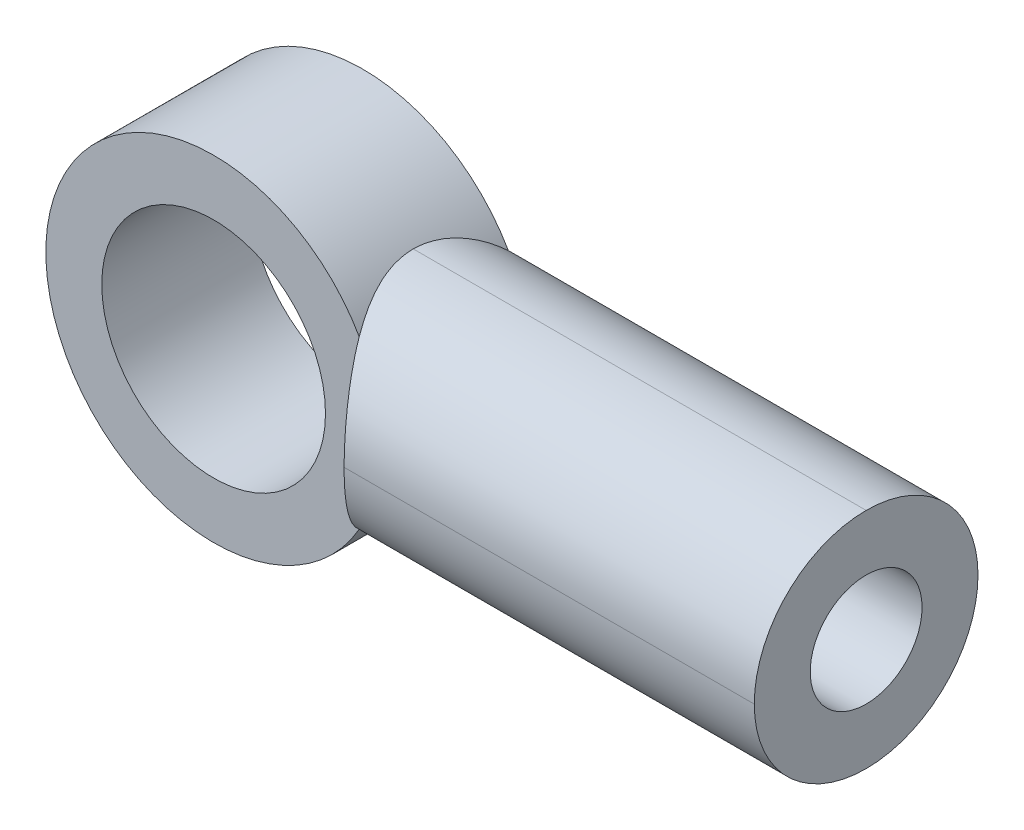
SolidWorks part; units mm, degrees
ref_plane "Top Plane" through (0, 0, 0) normal (0, 0, 1) x (1, 0, 0)
ref_plane "Right Plane" through (0, 0, 0) normal (0, 1, 0) x (1, 0, 0)
ref_plane "Front Plane" through (0, 0, 0) normal (1, 0, 0) x (0, 0, -1)
sketch "Sketch1" plane through (0, 0, 0) normal (0, 0, 1) x (1, 0, 0)
  line L0 (0, 0) -> (15.5, 0) construction
  line L1 (3.3541, -3) -> (15.5, -3)
  line L2 (15.5, -3) -> (15.5, 3)
  line L3 (3.3541, 3) -> (15.5, 3)
  line L4 (2.5981, -1.5) -> (15.5, -1.5) construction
  line L5 (2.5981, 1.5) -> (15.5, 1.5) construction
  circle A0 centre (0, 0) radius 3 construction
  arc A1 (3.3541, 3) -> (3.3541, -3) centre (0, 0) ccw
  point P12 (-4.5, 0)
  dimension "D1" = 6
  dimension "D2" = 9
  dimension "D3" = 6
  dimension "D4" = 3
  dimension "D5" = 20
extrude "Boss-Extrude1" add sketch "Sketch1" along normal mid plane 6
sketch "Sketch10" plane through (0, 0, 3) normal (0, 0, 1) x (1, 0, 0)
  circle A0 centre (0, 0) radius 3
  circle A1 centre (0, 0) radius 3 construction
extrude "Cut-Extrude1" cut sketch "Sketch10" against normal through all both and the other way through all
ref_plane "Plane1" through (-4.5, 0, 0) normal (-1, 0, 0) x (0, 0, 1)
sketch "Sketch11" plane through (15.5, 0, 0) normal (1, 0, 0) x (0, 0, -1)
  line L0 (0, 4.5) -> (0, -4.5) construction
  circle A0 centre (0, 0) radius 1.5
  dimension "D1" = 3
extrude "Cut-Extrude2" cut sketch "Sketch11" against normal offset from surface (10 mm away) 10 up to plane "Plane1"
fillet "Fillet1" radius 3 4 edges at (9.4271, -3, 3) (9.4271, -3, -3) (9.4271, 3, -3) (9.4271, 3, 3)
sketch "Sketch12" plane through (0, 0, 0) normal (0, 0, 1) x (1, 0, 0)
  circle A0 centre (0, 0) radius 4.5
  arc A1 (3.3541, 3) -> (3.3541, -3) centre (0, 0) ccw construction
extrude "Cut-Extrude3" cut sketch "Sketch12" against normal blind 10 from offset 2 offset against normal yes
mirror "Mirror1" about plane through (0, 0, 0) normal (0, 0, 1) of "Cut-Extrude3"
